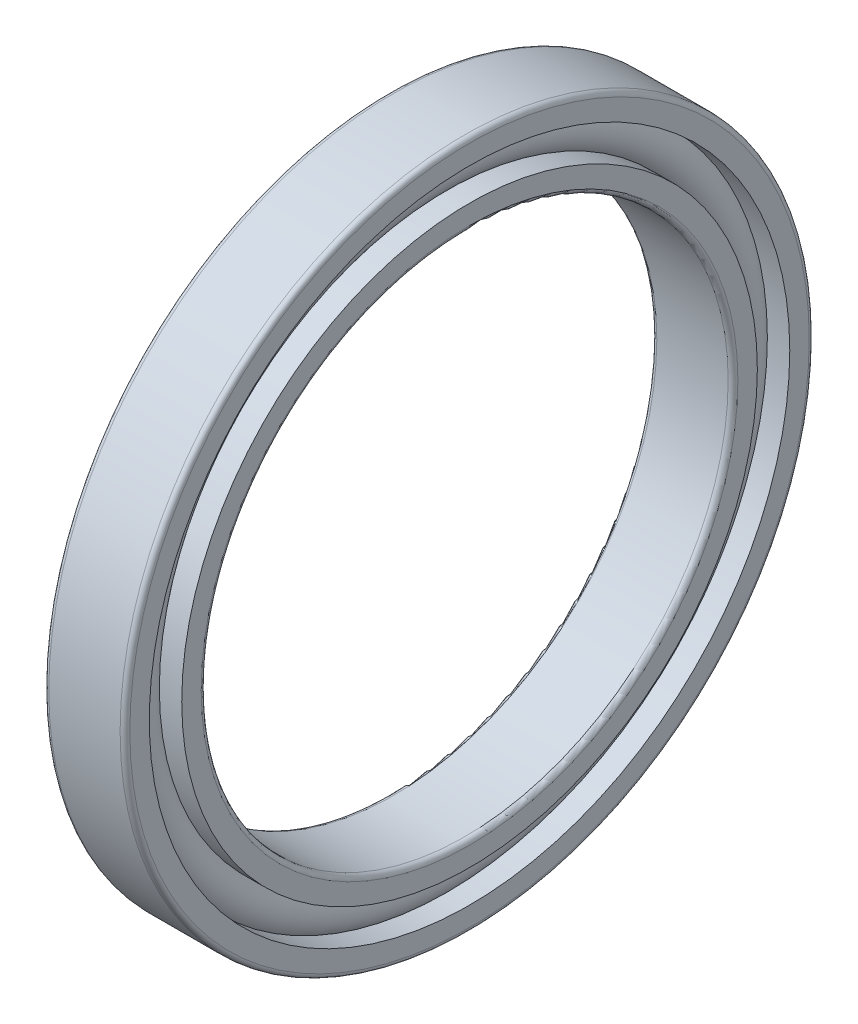
SolidWorks part; units mm, degrees
ref_plane "Plane1" through (0, 0, 0) normal (0, 0, 1) x (1, 0, 0)
ref_plane "Plane2" through (0, 0, 0) normal (0, 1, 0) x (1, 0, 0)
ref_plane "Plane3" through (0, 0, 0) normal (1, 0, 0) x (0, 0, -1)
sketch "Clipboard" plane through (0, 0, 0) normal (0, 0, 1) x (1, 0, 0)
  line L0 (-10, 0) -> (10, 0) construction
  line L1 (0, 0) -> (22.3471, -0.7804)
  line L2 (0, 0) -> (37.4772, 1.3087)
  line L3 (0, 0) -> (22.3471, -0.7804)
  line L4 (0, 0) -> (-22.3573, -0.3902)
  dimension "BallCLRad" = 37.5
  dimension "Count" = 2
  dimension "Show_count" = 2
  dimension "Max_count" = 2
  dimension "Min_count" = 1
sketch "CagSpiSke" plane through (0, 0, 0) normal (0, 0, 1) x (1, 0, 0)
  line L0 (0.3, 37) -> (0.3, 38)
  line L1 (0.3, 38) -> (-0.3, 38)
  line L2 (-0.3, 38) -> (-0.3, 37)
  line L3 (-0.3, 37) -> (0.3, 37)
  line L4 (-20.6375, 0) -> (20.6375, 0) construction
  line L5 (0, 0) -> (0, 23.7692) construction
  dimension "Thickness" = 0.6
  dimension "OD" = 76
  dimension "ID" = 74
revolve "CageSpine" add sketch "CagSpiSke" angle 0.001 about L4 reverse direction yes
ref_axis "Axis1" through (-50, 0, 0) along (1, 0, 0)
sketch "CagBalSke" plane through (0, 0, 0) normal (0, 0, 1) x (1, 0, 0)
  line L0 (-3.3, 37.5) -> (3.3, 37.5)
  line L1 (-1.905, 37.5) -> (1.905, 37.5) construction
  line L2 (-10, 0) -> (10, 0) construction
  line L3 (0, 0) -> (0, 24) construction
  arc A0 (3.3, 37.5) -> (-3.3, 37.5) centre (0, 37.5) cw
  dimension "CageWallOD" = 6.6
  dimension "BallCLRad" = 37.5
revolve "CageBall" [suppressed] add sketch "CagBalSke" angle 360 about L1 reverse direction yes
pattern_circular "CageBalls" [suppressed] count 2 every 180 about axis through (-50, 0, 0) along (1, 0, 0)
sketch "CagTrmODSke" plane through (0, 0, 0) normal (0, 0, 1) x (1, 0, 0)
  line L0 (3.301, 38) -> (3.301, 40.801)
  line L1 (3.301, 40.801) -> (-3.301, 40.801)
  line L2 (-3.301, 40.801) -> (-3.301, 38)
  line L3 (-3.301, 38) -> (3.301, 38)
  line L4 (-20.6375, 0) -> (20.6375, 0) construction
  line L5 (0, 0) -> (0, 25) construction
  dimension "Width" = 6.602
  dimension "ID" = 76
  dimension "OD" = 81.602
revolve "CageTrimOD" [suppressed] cut sketch "CagTrmODSke" angle 360 about L4 reverse direction yes
sketch "CagTrmIDSke" plane through (0, 0, 0) normal (0, 0, 1) x (1, 0, 0)
  line L0 (3.301, 34.201) -> (3.301, 37)
  line L1 (3.301, 37) -> (-3.301, 37)
  line L2 (-3.301, 37) -> (-3.301, 34.201)
  line L3 (-3.301, 34.201) -> (3.301, 34.201)
  line L4 (-20.6375, 0) -> (20.6375, 0) construction
  line L5 (0, 0) -> (0, 25) construction
  dimension "ID" = 68.402
  dimension "OD" = 74
  dimension "Width" = 6.602
revolve "CageTrimID" [suppressed] cut sketch "CagTrmIDSke" angle 360 about L4 reverse direction yes
sketch "BalSimSke" plane through (0, 0, 0) normal (0, 0, 1) x (1, 0, 0)
  line L0 (-10, 0) -> (10, 0) construction
  line L1 (-10, 37.5) -> (10, 37.5) construction
  line L2 (0, 0) -> (0, 23) construction
  circle A0 centre (0, 37.5) radius 3
  dimension "Ball_diameter" = 6
  dimension "BallCLRad" = 37.5
revolve "BallsSimplified" add sketch "BalSimSke" angle 360 about L0
sketch "BalDetSke" plane through (0, 0, 0) normal (0, 0, 1) x (1, 0, 0)
  line L0 (-3, 37.5) -> (3, 37.5)
  line L1 (-1.905, 37.5) -> (1.905, 37.5) construction
  line L2 (0, 0) -> (0, 25) construction
  arc A0 (3, 37.5) -> (-3, 37.5) centre (0, 37.5) cw
  dimension "Ball_diameter" = 6
  dimension "BallCLRad" = 37.5
revolve "BallDetailed" [suppressed] add sketch "BalDetSke" angle 360 about L1 reverse direction yes
sketch "InnRacSke" plane through (0, 0, 0) normal (0, 0, 1) x (1, 0, 0)
  line L0 (-2.2024, 35.5) -> (-5, 35.5)
  line L1 (-5, 35.5) -> (-5, 33.1)
  line L2 (-4.4, 32.5) -> (4.4, 32.5)
  line L3 (5, 33.1) -> (5, 35.5)
  line L4 (5, 35.5) -> (2.2024, 35.5)
  line L5 (-20.6375, 0) -> (20.6375, 0) construction
  line L6 (0, 0) -> (0, 30) construction
  arc A0 (-5, 33.1) -> (-4.4, 32.5) centre (-4.4, 33.1) ccw
  arc A1 (4.4, 32.5) -> (5, 33.1) centre (4.4, 33.1) ccw
  arc A2 (2.2024, 35.5) -> (-2.2024, 35.5) centre (0, 37.5) cw
  dimension "Fillet_radius" = 0.6
  dimension "Ball_diameter" = 5.95
  dimension "ID" = 65
  dimension "OD" = 71
  dimension "Width" = 10
  dimension "BallCLRad" = 37.5
revolve "InnerRace" add sketch "InnRacSke" angle 360 about L5 reverse direction yes
sketch "OutRacSke" plane through (0, 0, 0) normal (0, 0, 1) x (1, 0, 0)
  line L0 (-2.2024, 39.5) -> (-5, 39.5)
  line L1 (-5, 39.5) -> (-5, 41.9)
  line L2 (-4.4, 42.5) -> (4.4, 42.5)
  line L3 (5, 41.9) -> (5, 39.5)
  line L4 (5, 39.5) -> (2.2024, 39.5)
  line L5 (-20.6375, 0) -> (20.6375, 0) construction
  line L6 (0, 0) -> (0, 30) construction
  arc A0 (-5, 41.9) -> (-4.4, 42.5) centre (-4.4, 41.9) cw
  arc A1 (4.4, 42.5) -> (5, 41.9) centre (4.4, 41.9) cw
  arc A2 (2.2024, 39.5) -> (-2.2024, 39.5) centre (0, 37.5) ccw
  dimension "Fillet_radius" = 0.6
  dimension "Ball_diameter" = 5.95
  dimension "OD" = 85
  dimension "ID" = 79
  dimension "Width" = 10
  dimension "BallCLRad" = 37.5
revolve "OuterRace" add sketch "OutRacSke" angle 360 about L5 reverse direction yes
pattern_circular "BallsDetailed" [suppressed] count 2 every 180 about axis through (-50, 0, 0) along (1, 0, 0)
equation "\"BallCLRad@Clipboard\" = ( \"OD@OutRacSke\" + \"ID@InnRacSke\" ) / 4"
equation "\"BallCLRad@BalSimSke\" = \"BallCLRad@Clipboard\""
equation "\"BallCLRad@BalDetSke\" = \"BallCLRad@Clipboard\""
equation "\"BallCLRad@InnRacSke\" = \"BallCLRad@Clipboard\""
equation "\"BallCLRad@OutRacSke\" = \"BallCLRad@Clipboard\""
equation "\"Ball_diameter@InnRacSke\" = \"Ball_diameter@BalDetSke\" - 0.05"
equation "\"Ball_diameter@OutRacSke\" = \"Ball_diameter@BalDetSke\" - 0.05"
equation "\"Ball_diameter@BalSimSke\" = \"Ball_diameter@BalDetSke\""
equation "\"Width@OutRacSke\" = \"Width@InnRacSke\""
equation "\"Fillet_radius@OutRacSke\" = \"Fillet_radius@InnRacSke\""
equation "\"Max_count@Clipboard\" = int( 3.14159265 / atn(( \"Ball_diameter@BalDetSke\" / 2) / sqr( \"BallCLRad@Clipboard\"  *  \"BallCLRad@Clipboard\" - ( \"Ball_diameter@BalDetSke\" / 2) *  ( \"Ball_diameter@BalDetSke\" / 2))))"
equation "\"Max_count@Clipboard\" = ((sgn( \"Max_count@Clipboard\" - \"Count@Clipboard\" )-1)*( \"Max_count@Clipboard\" - \"Count@Clipboard\" ))/-2+ \"Count@Clipboard\""
equation "\"Count@BallsDetailed\" = int( \"Show_count@Clipboard\" ) "
equation "\"Count@BallsDetailed\" = ((sgn( \"Count@BallsDetailed\" - \"Max_count@Clipboard\" )-1)*( \"Count@BallsDetailed\" - \"Max_count@Clipboard\" ))/-2+ \"Max_count@Clipboard\""
equation "\"Count@BallsDetailed\" = ((sgn( \"Count@BallsDetailed\" - \"Min_count@Clipboard\" )+1)*( \"Count@BallsDetailed\" - \"Min_count@Clipboard\"))/2 +\"Min_count@Clipboard\""
equation "\"Angle@BallsDetailed\" = 360.0 / \"Max_count@Clipboard\""
equation "\"BallCLRad@CagBalSke\" = \"BallCLRad@Clipboard\""
equation "\"Count@CageBalls\" = \"Count@BallsDetailed\""
equation "\"Angle@CageBalls\" = \"Angle@BallsDetailed\""
equation "\"Angle@CageSpine\" =  \"Angle@CageBalls\" * ( \"Count@CageBalls\" -1 + int( \"Count@CageBalls\" / \"Max_count@Clipboard\" ) )  + 0.001 -  int( \"Count@CageBalls\" / \"Max_count@Clipboard\" ) * 0.001"
equation "\"Angle@CageSpine\" =  \"Angle@CageSpine\" * int( \"Min_count@Clipboard\" / 2) + int(1 / \"Min_count@Clipboard\")  * 0.001"
equation "\"CageWallOD@CagBalSke\" =  \"Ball_diameter@BalDetSke\" * 1.1"
equation "\"Thickness@CagSpiSke\" =  \"Ball_diameter@BalDetSke\" * 0.1"
equation "\"OD@CagTrmODSke\" = \"BallCLRad@Clipboard\" * 2 + \"CageWallOD@CagBalSke\" + 0.002"
equation "\"ID@CagTrmODSke\" = \"BallCLRad@Clipboard\" * 2 + \"Ball_diameter@BalDetSke\" / 6"
equation "\"OD@CagTrmIDSke\" = \"BallCLRad@Clipboard\" * 2 - \"Ball_diameter@BalDetSke\" / 6"
equation "\"ID@CagTrmIDSke\" = \"BallCLRad@Clipboard\" * 2 - \"CageWallOD@CagBalSke\" + 0.002"
equation "\"OD@CagSpiSke\" = \"ID@CagTrmODSke\""
equation "\"ID@CagSpiSke\" = \"OD@CagTrmIDSke\""
equation "\"Width@CagTrmODSke\" = \"CageWallOD@CagBalSke\" + 0.002"
equation "\"Width@CagTrmIDSke\" = \"CageWallOD@CagBalSke\" + 0.002"
